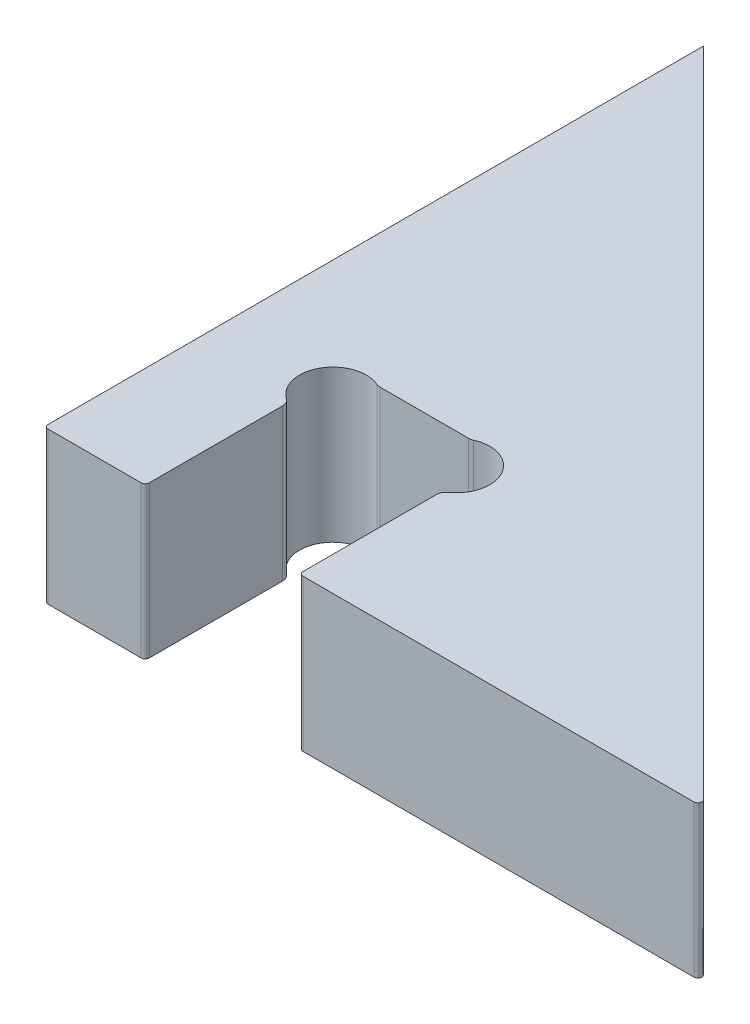
SolidWorks part; units mm, degrees
ref_plane "Front Plane" through (0, 0, 0) normal (0, 0, 1) x (1, 0, 0)
ref_plane "Top Plane" through (0, 0, 0) normal (0, 1, 0) x (1, 0, 0)
ref_plane "Right Plane" through (0, 0, 0) normal (1, 0, 0) x (0, 0, -1)
other "Bounding Box"
ref_plane "Default Plane" through (13.8565, 3.175, 6.7999) normal (0, -1, 0) x (-1, 0, 0)
sketch "Sketch1" plane through (0, 0, 0) normal (0, 1, 0) x (1, 0, 0)
  line L0 (0, 0) -> (0, -25.4)
  line L1 (0, -25.4) -> (6.35, -25.4)
  line L2 (6.35, -25.4) -> (6.35, -12.7)
  line L3 (6.35, -12.7) -> (16.002, -12.7)
  line L4 (16.002, -12.7) -> (16.002, -25.4)
  line L5 (16.002, -25.4) -> (22.352, -19.05)
  line L6 (22.352, -19.05) -> (22.352, -6.35)
  line L8 (0, -12.7) -> (6.35, -12.7) construction
  line L9 (16.002, -12.7) -> (22.352, -12.7) construction
  line L10 (22.352, -6.35) -> (16.002, 0)
  line L11 (16.002, 0) -> (0, 0)
  dimension "D1" = 9.652
  dimension "D2" = 25.4
  dimension "D3" = 45
  dimension "D4" = 6.35
  dimension "D5" = 12.7
extrude "Boss-Extrude1" add sketch "Sketch1" along normal blind 9.525
sketch "Sketch2" plane through (0, 9.525, 0) normal (0, 1, 0) x (1, 0, 0)
  line L0 (16.002, 0) -> (41.402, -25.4)
  line L1 (41.402, -25.4) -> (16.002, -25.4)
  line L5 (22.352, -6.35) -> (16.002, 0) construction
  line L7 (0, 0) -> (0, 16.002)
  line L11 (0, 16.002) -> (16.002, 0)
  line L12 (16.002, -25.4) -> (16.002, -12.7)
  line L13 (16.002, -12.7) -> (0, 0)
extrude "Boss-Extrude2" add sketch "Sketch2" against normal through all
sketch "Sketch3" [suppressed] plane through (0, 9.525, 0) normal (0, 1, 0) x (1, 0, 0)
  line L2 (15.875, -12.7) -> (15.875, 0) construction
  line L6 (19.05, -3.175) -> (24.13, -3.175) construction
  line L7 (22.225, -6.35) -> (15.875, 0) construction
  line L8 (15.875, 0) -> (18.0026, 2.3567)
  line L9 (15.875, 0) -> (15.875, -3.175)
  line L10 (30.2574, -8.7067) -> (22.225, -17.6042)
  line L11 (22.225, -31.75) -> (22.225, -6.35) construction
  line L12 (22.225, -17.6042) -> (22.225, -11.2072)
  circle A1 centre (24.13, -3.175) radius 2.9845
  arc A2 (15.875, -3.175) -> (22.225, -11.2072) centre (24.13, -3.175) ccw
  arc A3 (30.2574, -8.7067) -> (18.0026, 2.3567) centre (24.13, -3.175) ccw
  dimension "D1" = 8.255
  dimension "D2" = 5.969
extrude "Boss-Extrude3" [suppressed] add sketch "Sketch3" against normal through all
sketch "Sketch5" plane through (0, 9.525, 0) normal (0, 1, 0) x (1, 0, 0)
  line L0 (6.35, -12.7) -> (7.3025, -14.5665) construction
  line L1 (7.3025, -14.5665) -> (8.255, -12.7) construction
  line L2 (6.35, -12.7) -> (16.002, -12.7) construction
  line L3 (14.097, -12.7) -> (15.0495, -14.5665) construction
  line L4 (15.0495, -14.5665) -> (16.002, -12.7) construction
  line L5 (7.3025, -14.5665) -> (15.0495, -14.5665) construction
  circle A0 centre (15.0495, -14.5665) radius 2.0955
  circle A1 centre (7.3025, -14.5665) radius 2.0955
  dimension "D1" = 4.191
  dimension "D2" = 7.747
extrude "Cut-Extrude2" cut sketch "Sketch5" against normal through all
fillet "Fillet1" radius 0.635 4 edges at (16.002, 4.7625, 16.433) (6.35, 4.7625, 16.433) (14.097, 4.7625, 12.7) (8.255, 4.7625, 12.7)
sketch "Sketch6" [suppressed] plane through (0, 9.525, 0) normal (0, 1, 0) x (1, 0, 0)
  line L0 (6.35, -38.1) -> (6.35, -16.8632) construction
  line L1 (0, -38.1) -> (6.35, -38.1)
  line L2 (0, -38.1) -> (0, -19.05)
  line L3 (0, -19.05) -> (6.35, -19.05)
  line L4 (6.35, -38.1) -> (6.35, -19.05)
  line L5 (0, -38.1) -> (6.35, -19.05) construction
  line L6 (0, -19.05) -> (6.35, -38.1) construction
  point P4 (3.175, -28.575)
  dimension "D1" = 19.05
extrude "Cut-Extrude3" [suppressed] cut sketch "Sketch6" against normal through all
fillet "Fillet2" [suppressed] radius 2.54
fillet "Fillet4" radius 0.254 4 edges at (41.402, 4.7625, 25.4) (6.35, 4.7625, 25.4) (16.002, 4.7625, 25.4) (0, 4.7625, 25.4)
fillet "Fillet5" [suppressed] radius 0.254
fillet "Fillet6" [suppressed] radius 0.254
fillet "Fillet7" [suppressed] radius 2.54
